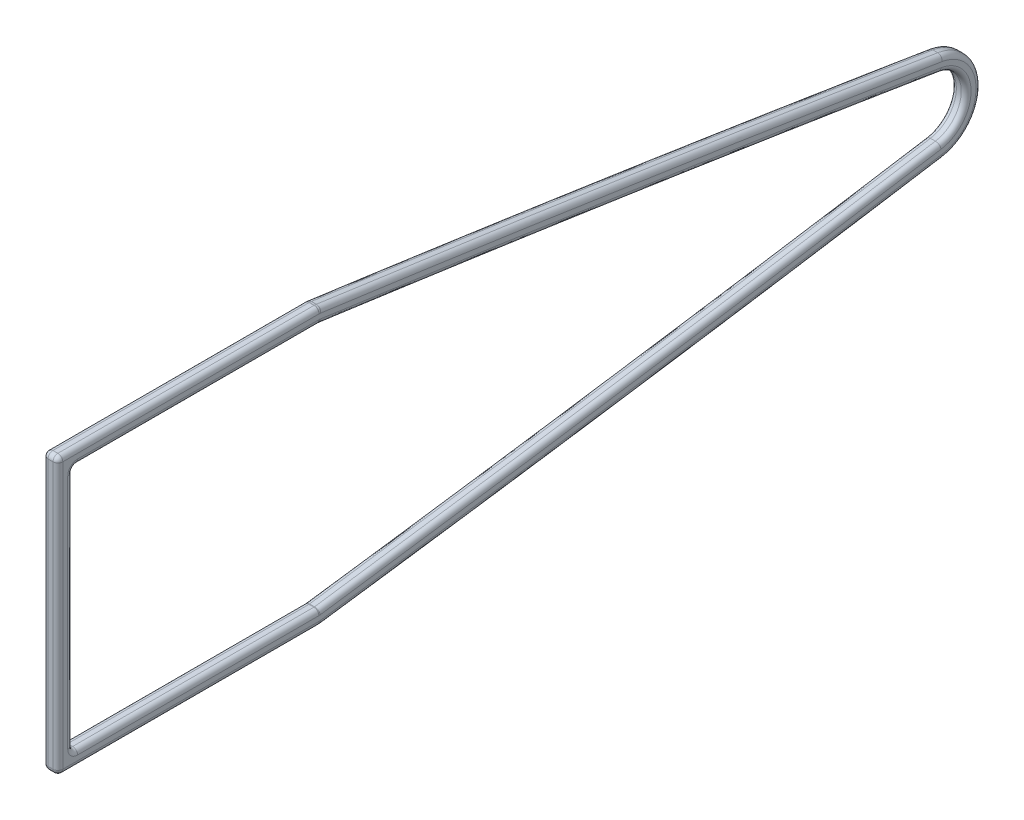
SolidWorks part; units mm, degrees
material "BUTYL"
ref_plane "Front Plane" through (0, 0, 0) normal (0, 0, 1) x (1, 0, 0)
ref_plane "Top Plane" through (0, 0, 0) normal (0, 1, 0) x (1, 0, 0)
ref_plane "Right Plane" through (0, 0, 0) normal (1, 0, 0) x (0, 0, -1)
sketch "Sketch2" plane through (0, 0, 0) normal (1, 0, 0) x (0, 0, -1)
  line L0 (-11.501, 0) -> (26.599, 0) construction
  line L1 (-5.151, 5.588) -> (-17.089, 5.588)
  line L2 (-5.151, -6.35) -> (-17.851, -6.35)
  line L3 (-5.151, -6.35) -> (-5.151, 6.35)
  line L4 (-5.151, 6.35) -> (-17.851, 6.35)
  line L5 (-17.851, -6.35) -> (-17.851, 6.35)
  line L6 (-5.151, -6.35) -> (-17.851, 6.35) construction
  line L7 (-5.151, 6.35) -> (-17.851, -6.35) construction
  line L8 (-17.089, -5.588) -> (-17.089, 5.588)
  line L9 (-5.151, -5.588) -> (-17.089, -5.588)
  line L10 (-5.151, 7.112) -> (-18.613, 7.112)
  line L11 (-18.613, -7.112) -> (-18.613, 7.112)
  line L12 (-5.151, -7.112) -> (-18.613, -7.112)
  line L13 (-5.151, 7.112) -> (-5.0478, 7.105)
  line L14 (-5.151, -7.112) -> (-5.0476, -7.105)
  circle A0 centre (26.599, 0) radius 1.5875
  circle A1 centre (26.599, 0) radius 0.8255
  circle A2 centre (26.599, 0) radius 2.3495
  spline S0 degree 2 poles (-5.151, 6.35) (10.8806, 4.1585) (26.8532, 1.567) knots 0 0 0 1 1 1
  spline S1 degree 2 poles (-5.151, -6.35) (10.8799, -4.1549) (26.8529, -1.5671) knots 0 0 0 1 1 1
  spline S2 degree 1 poles (-5.0478, 7.105) (26.9753, 2.3192) knots 0 0 1 1 construction
  spline S3 degree 3 poles (-5.0478, 7.105) (5.6456, 5.6432) (16.3217, 4.0477) (26.9753, 2.3192) knots 0 0 0 0 1 1 1 1
  spline S4 degree 1 poles (-5.2544, -5.595) (26.731, -0.8149) knots 0 0 1 1 construction
  spline S5 degree 3 poles (-5.2544, -5.595) (5.4262, -4.1326) (16.0896, -2.539) (26.731, -0.8149) knots 0 0 0 0 1 1 1 1
  spline S6 degree 1 poles (-5.2542, 5.595) (26.7312, 0.8148) knots 0 0 1 1 construction
  spline S7 degree 3 poles (-5.2542, 5.595) (5.4267, 4.135) (16.0901, 2.5413) (26.7312, 0.8148) knots 0 0 0 0 1 1 1 1
  spline S8 degree 1 poles (-5.0476, -7.105) (26.9747, -2.3193) knots 0 0 1 1 construction
  spline S9 degree 3 poles (-5.0476, -7.105) (5.6452, -5.6408) (16.321, -4.0453) (26.9747, -2.3193) knots 0 0 0 0 1 1 1 1
  point P9 (0, 0)
  point P19 (0, 0)
  dimension "D1" = 3.175
  dimension "D2" = 12.7
  dimension "D3" = 4.8006
  dimension "D4" = 4.8006
  dimension "D7" = 38.1
  dimension "D5" = 0.762
  dimension "D6" = 0.762
extrude "Boss-Extrude1" add sketch "Sketch2" along normal blind 0.762
fillet "Fillet1" radius 0.254 38 edges at (0.381, -6.35, 5.151) (0.381, -6.35, 17.851) (0.381, 6.35, 17.851) (0.381, 7.112, 18.613) (0.381, -7.112, 18.613) (0.381, 6.35, 5.151) (0, 6.35, 11.501) (0.762, 6.35, 11.501) (0, 0, 17.851) (0.762, 0, 17.851) (0, -6.35, 11.501) (0.762, -6.35, 11.501) (0, -0.0002, -28.1865) (0.762, -0.0002, -28.1865) (0, -7.112, 11.882) (0.762, -7.112, 11.882) (0, 0, 18.613) (0.762, 0, 18.613) (0, 7.112, 11.882) (0.762, 7.112, 11.882) (0, -0.0003, -28.9485) (0.762, -0.0003, -28.9485) (0.381, 7.105, 5.0478) (0.381, 7.112, 5.151) (0.381, -7.112, 5.151) (0.381, -7.105, 5.0476) (0, -7.1085, 5.0993) (0.762, -7.1085, 5.0993) (0, 7.1085, 5.0994) (0.762, 7.1085, 5.0994)
equation "\"PegWidth\"=0.125"
equation "\"PegSpread\"=20"
equation "\"D1@Sketch2\"=\"PegWidth\""
equation "\"PegCatchWidth\"=0.5"
equation "\"D2@Sketch2\"=\"PegCatchWidth\""
equation "\"SplineWidth\"=0.189"
equation "\"D3@Sketch2\"=\"SplineWidth\""
equation "\"D4@Sketch2\"=\"SplineWidth\""
equation "\"Height\"=0.03"
equation "\"D1@Boss-Extrude1\"=\"Height\""
